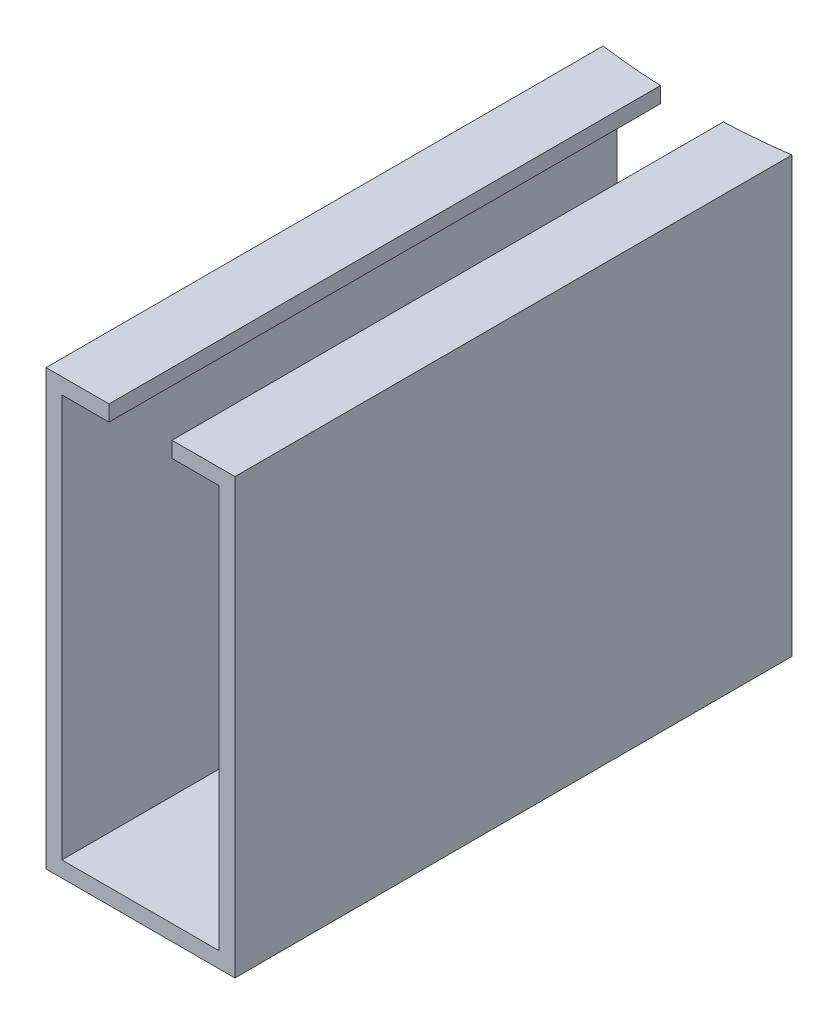
SolidWorks part; units mm, degrees
material "ABS"
ref_plane "正面" through (0, 0, 0) normal (0, 0, 1) x (1, 0, 0)
ref_plane "平面" through (0, 0, 0) normal (0, 1, 0) x (1, 0, 0)
ref_plane "右側面" through (0, 0, 0) normal (1, 0, 0) x (0, 0, -1)
sketch "ｽｹｯﾁ1" plane through (0, 0, 0) normal (0, 0, 1) x (1, 0, 0)
  line L0 (0, 0) -> (5, 0)
  line L1 (0, 0) -> (0, 12.8)
  line L3 (-0.5, 12.8) -> (-0.5, -0.5)
  line L4 (-0.5, -0.5) -> (5.5, -0.5)
  line L5 (5.5, -0.5) -> (5.5, 12.8)
  line L7 (5, 12.8) -> (5, 0)
  line L8 (-0.5, 12.8) -> (-0.5, 13.3)
  line L9 (-0.5, 13.3) -> (1.5, 13.3)
  line L10 (1.5, 13.3) -> (1.5, 12.8)
  line L11 (1.5, 12.8) -> (0, 12.8)
  line L12 (5.5, 12.8) -> (5.5, 13.3)
  line L13 (5.5, 13.3) -> (3.5, 13.3)
  line L14 (3.5, 13.3) -> (3.5, 12.8)
  line L15 (3.5, 12.8) -> (5, 12.8)
  dimension "D1" = 5
  dimension "D2" = 12.8
  dimension "D3" = 0.5
  dimension "D4" = 13.3
  dimension "D5" = 6
  dimension "D6" = 13.3
  dimension "D7" = 0.5
  dimension "D8" = 0.5
  dimension "D9" = 2
  dimension "D10" = 2
  dimension "D11" = 0.5
extrude "ﾎﾞｽ - 押し出し1" add sketch "ｽｹｯﾁ1" along normal blind 40
sketch "ｽｹｯﾁ2" plane through (0, -0.5, 0) normal (0, -1, 0) x (1, 0, 0)
  line L0 (2.5, 40) -> (2.5, 0)
  line L1 (-0.5, 40) -> (5.5, 40) construction
  line L2 (-0.5, 0) -> (5.5, 0) construction
  circle A0 centre (2.5, 0) radius 22.5
  dimension "D1" = 45
extrude "ｶｯﾄ - 押し出し1" cut sketch "ｽｹｯﾁ2" against normal blind 40 contours A0
